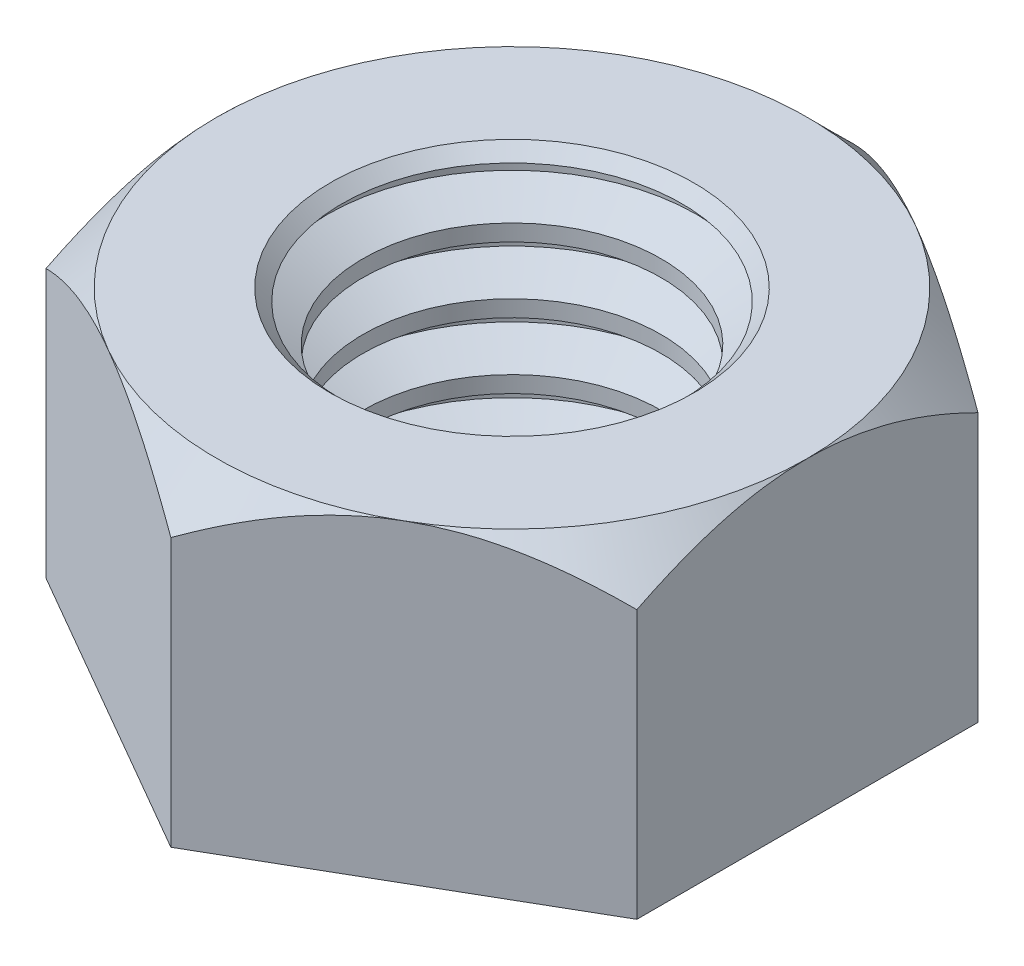
SolidWorks part; units mm, degrees
ref_plane "Front" through (0, 0, 0) normal (0, 0, 1) x (1, 0, 0)
ref_plane "Top" through (0, 0, 0) normal (0, 1, 0) x (1, 0, 0)
ref_plane "Right" through (0, 0, 0) normal (1, 0, 0) x (0, 0, -1)
sketch "Sketch1" plane through (0, 0, 0) normal (0, 1, 0) x (1, 0, 0)
  line L1 (0, 7.3323) -> (-6.35, 3.6662)
  line L2 (-6.35, 3.6662) -> (-6.35, -3.6662)
  line L3 (-6.35, -3.6662) -> (0, -7.3323)
  line L4 (0, -7.3323) -> (6.35, -3.6662)
  line L5 (6.35, -3.6662) -> (6.35, 3.6662)
  line L6 (6.35, 3.6662) -> (0, 7.3323)
  circle A0 centre (0, 0) radius 6.35 construction
extrude "Extrude1" add sketch "Sketch1" along normal blind 6.7469
sketch "Sketch3" plane through (0, 0, 0) normal (1, 0, 0) x (0, 0, -1)
  line L0 (6.35, 6.7469) -> (7.3323, 5.7645)
  line L1 (3.6662, 6.7469) -> (7.3323, 6.7469) construction
  line L2 (7.3323, 6.7469) -> (7.3323, 0) construction
  line L3 (7.3323, 5.7645) -> (7.3323, 6.7469)
  line L4 (7.3323, 6.7469) -> (6.35, 6.7469)
  line L5 (0, 0.542) -> (0, -0.542) construction
  dimension "D1" = 45
  dimension "D2" = 12.7
revolve "Cut-Revolve2" cut sketch "Sketch3" angle 360 about L5
sketch "Sketch2" plane through (0, 0, 0) normal (0, 0, 1) x (1, 0, 0)
  line L0 (0, 1.6636) -> (0, -0.3796) construction
  line L1 (0, 6.7469) -> (3.205, 6.7469)
  line L3 (0, 6.7469) -> (6.35, 6.7469) construction
  line L4 (0, 5.3358) -> (3.205, 5.3358)
  line L5 (3.205, 6.7469) -> (3.9688, 6.3059)
  line L6 (3.9688, 6.3059) -> (3.9688, 6.1295)
  line L7 (3.9688, 6.1295) -> (3.205, 5.6885)
  line L9 (3.205, 5.3358) -> (3.205, 5.6885)
  line L10 (0, 5.3358) -> (0, 6.7469)
  line L11 (3.205, 6.7469) -> (3.205, 5.6885) construction
  line L12 (3.9688, 6.2177) -> (3.205, 6.2177) construction
  dimension "D1" = 60
  dimension "Pitch" = 1.4111
  dimension "Major Dia." = 7.9375
  dimension "D5" = 0.1764
  dimension "D2" = 0.3528
revolve "Cut-Revolve1" cut sketch "Sketch2" angle 360 about L0
pattern_linear "LPattern2" count 5 spacing 1.4111 along (0, -1, 0) of "Cut-Revolve1"
chamfer "Chamfer1" distance 0.7056 angle 45 1 edges at (0, 6.7469, 3.205) first distance on face at (0, 6.7469, 0)
equation "\"D5@Sketch2\"=\"Pitch@Sketch2\"/8"
equation "\"D2@Sketch2\"=\"Pitch@Sketch2\"/4"
equation "\"D3@LPattern2\"=\"Pitch@Sketch2\""
equation "\"D1@LPattern2\"=int(\"Height@Extrude1\"/\"Pitch@Sketch2\")+1"
equation "\"D2@Sketch3\"=\"Hex Flats@Sketch1\""
equation "\"D1@Chamfer1\"=\"Pitch@Sketch2\"/2"
